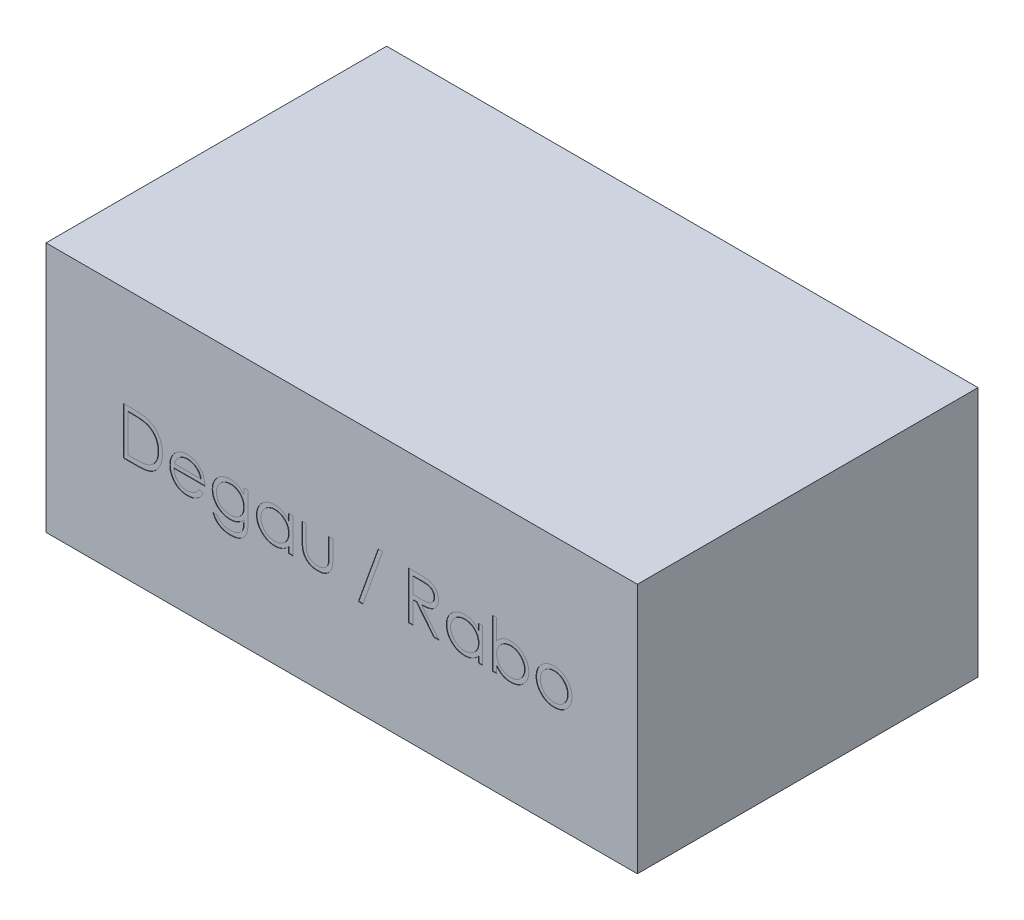
SolidWorks part; units mm, degrees
ref_plane "Front" through (0, 0, 0) normal (0, 0, 1) x (1, 0, 0)
ref_plane "Top" through (0, 0, 0) normal (0, 1, 0) x (1, 0, 0)
ref_plane "Right" through (0, 0, 0) normal (1, 0, 0) x (0, 0, -1)
sketch "Esquisse1" plane through (0, 0, 0) normal (0, 0, 1) x (1, 0, 0)
  line L1 (0, 0) -> (1250, 0)
  line L2 (0, 0) -> (0, 530)
  line L3 (0, 530) -> (1250, 530)
  line L4 (1250, 0) -> (1250, 530)
  dimension "D1" = 1250
  dimension "D2" = 530
extrude "Boss.-Extru.1" add sketch "Esquisse1" along normal blind 720
sketch "Esquisse2" plane through (0, 0, 720) normal (0, 0, 1) x (1, 0, 0)
  text T0 "Degau / Rabo" font "Century Gothic" height 100
  point P1 (215.8689, 219.1825)
  point P2 (170.6967, 212.7293)
  point P3 (0, 0)
  point P4 (128.1057, 241.1233)
  point P5 (151.3371, 217.8918)
extrude "Enlèv. mat.-Extru.1" cut sketch "Esquisse2" against normal blind 1
